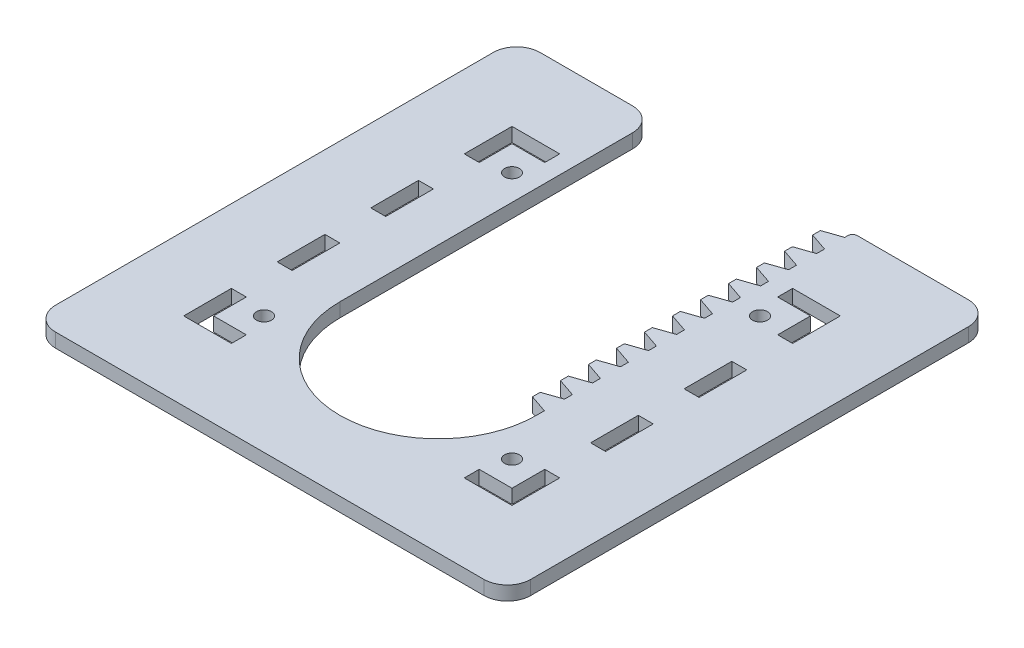
SolidWorks part; units mm, degrees
ref_plane "Front Plane" through (0, 0, 0) normal (0, 0, 1) x (1, 0, 0)
ref_plane "Top Plane" through (0, 0, 0) normal (0, 1, 0) x (1, 0, 0)
ref_plane "Right Plane" through (0, 0, 0) normal (1, 0, 0) x (0, 0, -1)
sketch "Sketch1" plane through (0, 0, 0) normal (0, 1, 0) x (1, 0, 0)
  line L0 (0, 0) -> (0, 21) construction
  line L1 (17.1887, 0) -> (0, 0) construction
  line L2 (21.0585, 3.843) -> (17.1887, 5.1665) construction
  line L3 (17.1887, 5.1665) -> (17.1887, 6.8335) construction
  line L4 (17.1887, 6.8335) -> (21.0585, 8.157) construction
  line L5 (21.0585, 9.843) -> (21.0585, 8.157) construction
  line L6 (21.0585, 9.843) -> (17.1887, 11.1665) construction
  line L7 (17.1887, 11.1665) -> (17.1887, 12.8335) construction
  line L8 (17.1887, 12.8335) -> (21.0585, 14.157) construction
  line L9 (21.0585, 15.843) -> (21.0585, 14.157) construction
  line L10 (21.0585, 15.843) -> (17.1887, 17.1665) construction
  line L11 (17.1887, 17.1665) -> (17.1887, 18.8335) construction
  line L12 (17.1887, 18.8335) -> (21.0585, 20.157) construction
  line L13 (21.0585, 21.843) -> (21.0585, 20.157) construction
  line L14 (21.0585, 21.843) -> (17.1887, 23.1665) construction
  line L15 (17.1887, 23.1665) -> (17.1887, 24.8335) construction
  line L16 (17.1887, 24.8335) -> (21.0585, 26.157) construction
  line L17 (21.0585, 27.843) -> (21.0585, 26.157) construction
  line L18 (21.0585, 27.843) -> (17.1887, 29.1665) construction
  line L19 (17.1887, 29.1665) -> (17.1887, 30.8335) construction
  line L20 (17.1887, 30.8335) -> (21.0585, 32.157) construction
  line L21 (21.0585, 33.843) -> (21.0585, 32.157) construction
  line L22 (21.0585, 33.843) -> (17.1887, 35.1665) construction
  line L23 (17.1887, 35.1665) -> (17.1887, 36.8335) construction
  line L24 (17.1887, 36.8335) -> (21.0585, 38.157) construction
  line L25 (21.0585, 39.843) -> (21.0585, 38.157) construction
  line L26 (21.0585, 39.843) -> (17.1887, 41.1665) construction
  line L27 (17.1887, 41.1665) -> (17.1887, 42.8335) construction
  line L28 (17.1887, 42.8335) -> (21.0585, 44.157) construction
  line L29 (21.0585, 45.843) -> (21.0585, 44.157) construction
  line L30 (21.0585, 45.843) -> (17.1887, 47.1665) construction
  line L31 (17.1887, 47.1665) -> (17.1887, 48.8335) construction
  line L32 (17.1887, 48.8335) -> (21.0585, 50.157) construction
  line L33 (21.0585, 51.843) -> (21.0585, 50.157) construction
  line L34 (21.0585, 51.843) -> (17.1887, 53.1665) construction
  line L35 (17.1887, 53.1665) -> (17.1887, 54.8335) construction
  line L36 (17.1887, 54.8335) -> (21.0585, 56.157) construction
  line L37 (21.0585, 57.843) -> (21.0585, 56.157) construction
  line L38 (21.0585, 57.843) -> (17.1887, 59.1665) construction
  line L39 (17.1887, 59.1665) -> (17.1887, 60.8335) construction
  line L40 (17.1887, 60.8335) -> (21.0585, 62.157) construction
  line L41 (21.0585, 62.157) -> (21.0585, 62.843) construction
  line L42 (45.8722, 63.843) -> (22.0585, 63.843) construction
  line L43 (50.8722, -34.9014) -> (50.8722, 58.843) construction
  line L44 (45.8722, -39.9014) -> (-45.8722, -39.9014) construction
  line L45 (-50.8722, 58.843) -> (-50.8722, -34.9014) construction
  line L46 (-45.8722, 63.843) -> (-22.0585, 63.843) construction
  line L47 (-21.0585, -3.843) -> (-21.0585, 62.843) construction
  line L48 (21.0585, -2.157) -> (21.0585, -3.843) construction
  line L49 (21.0585, -2.157) -> (17.1887, -0.8335) construction
  line L50 (17.1887, -0.8335) -> (17.1887, 0.8335) construction
  line L51 (17.1887, 0.8335) -> (21.0585, 2.157) construction
  line L52 (21.0585, 3.843) -> (21.0585, 2.157) construction
  line L53 (21.0585, 3.843) -> (17.1887, 5.1665)
  line L54 (17.1887, 5.1665) -> (17.1887, 6.8335)
  line L55 (17.1887, 6.8335) -> (21.0585, 8.157)
  line L56 (21.0585, 9.843) -> (21.0585, 8.157)
  line L57 (21.0585, 9.843) -> (17.1887, 11.1665)
  line L58 (17.1887, 11.1665) -> (17.1887, 12.8335)
  line L59 (17.1887, 12.8335) -> (21.0585, 14.157)
  line L60 (21.0585, 15.843) -> (21.0585, 14.157)
  line L61 (21.0585, 15.843) -> (17.1887, 17.1665)
  line L62 (17.1887, 17.1665) -> (17.1887, 18.8335)
  line L63 (17.1887, 18.8335) -> (21.0585, 20.157)
  line L64 (21.0585, 21.843) -> (21.0585, 20.157)
  line L65 (21.0585, 21.843) -> (17.1887, 23.1665)
  line L66 (17.1887, 23.1665) -> (17.1887, 24.8335)
  line L67 (17.1887, 24.8335) -> (21.0585, 26.157)
  line L68 (21.0585, 27.843) -> (21.0585, 26.157)
  line L69 (21.0585, 27.843) -> (17.1887, 29.1665)
  line L70 (17.1887, 29.1665) -> (17.1887, 30.8335)
  line L71 (17.1887, 30.8335) -> (21.0585, 32.157)
  line L72 (21.0585, 33.843) -> (21.0585, 32.157)
  line L73 (21.0585, 33.843) -> (17.1887, 35.1665)
  line L74 (17.1887, 35.1665) -> (17.1887, 36.8335)
  line L75 (17.1887, 36.8335) -> (21.0585, 38.157)
  line L76 (21.0585, 39.843) -> (21.0585, 38.157)
  line L77 (21.0585, 39.843) -> (17.1887, 41.1665)
  line L78 (17.1887, 41.1665) -> (17.1887, 42.8335)
  line L79 (17.1887, 42.8335) -> (21.0585, 44.157)
  line L80 (21.0585, 45.843) -> (21.0585, 44.157)
  line L81 (21.0585, 45.843) -> (17.1887, 47.1665)
  line L82 (17.1887, 47.1665) -> (17.1887, 48.8335)
  line L83 (17.1887, 48.8335) -> (21.0585, 50.157)
  line L84 (21.0585, 51.843) -> (21.0585, 50.157)
  line L85 (21.0585, 51.843) -> (17.1887, 53.1665)
  line L86 (17.1887, 53.1665) -> (17.1887, 54.8335)
  line L87 (17.1887, 54.8335) -> (21.0585, 56.157)
  line L88 (21.0585, 57.843) -> (21.0585, 56.157)
  line L89 (21.0585, 57.843) -> (17.1887, 59.1665)
  line L90 (17.1887, 59.1665) -> (17.1887, 60.8335)
  line L91 (17.1887, 60.8335) -> (21.0585, 62.157)
  line L92 (21.0585, 62.157) -> (21.0585, 62.843)
  line L93 (45.8722, 63.843) -> (22.0585, 63.843)
  line L94 (50.8722, -34.9014) -> (50.8722, 58.843)
  line L95 (45.8722, -39.9014) -> (-45.8722, -39.9014)
  line L96 (-50.8722, 58.843) -> (-50.8722, -34.9014)
  line L97 (-45.8722, 63.843) -> (-26.0585, 63.843)
  line L98 (-21.0585, -3.843) -> (-21.0585, 58.843)
  line L99 (21.0585, -2.157) -> (21.0585, -3.843)
  line L100 (21.0585, -2.157) -> (17.1887, -0.8335)
  line L101 (17.1887, -0.8335) -> (17.1887, 0.8335)
  line L102 (17.1887, 0.8335) -> (21.0585, 2.157)
  line L103 (21.0585, 3.843) -> (21.0585, 2.157)
  line L104 (0, 63.843) -> (0, -39.9014) construction
  line L105 (-51.8722, 11.9708) -> (51.8722, 11.9708) construction
  line L106 (0, 11.9708) -> (-51.8722, -39.9014) construction
  line L107 (51.8722, -24.9014) -> (-51.8722, -24.9014) construction
  line L108 (-36.8722, -39.9014) -> (-36.8722, 63.843) construction
  line L109 (36.8722, -39.9014) -> (36.8722, 63.843) construction
  line L110 (45.8722, -39.9014) -> (51.8722, -39.9014) construction
  line L111 (51.8722, -39.9014) -> (51.8722, 63.843) construction
  line L112 (51.8722, 63.843) -> (-51.8722, 63.843) construction
  line L113 (17.1887, 60) -> (0, 60) construction
  line L114 (-51.8722, 63.843) -> (-51.8722, -39.9014) construction
  line L115 (-51.8722, -39.9014) -> (-45.8722, -39.9014) construction
  circle A0 centre (0, 0) radius 21 construction
  circle A1 centre (0, 60) radius 21 construction
  arc A2 (22.0585, 63.843) -> (21.0585, 62.843) centre (22.0585, 62.843) ccw construction
  arc A3 (50.8722, 58.843) -> (45.8722, 63.843) centre (45.8722, 58.843) ccw construction
  arc A4 (45.8722, -39.9014) -> (50.8722, -34.9014) centre (45.8722, -34.9014) ccw construction
  arc A5 (-50.8722, -34.9014) -> (-45.8722, -39.9014) centre (-45.8722, -34.9014) ccw construction
  arc A6 (-45.8722, 63.843) -> (-50.8722, 58.843) centre (-45.8722, 58.843) ccw construction
  arc A8 (-21.0585, -3.843) -> (21.0585, -3.843) centre (0, -3.843) ccw construction
  arc A9 (22.0585, 63.843) -> (21.0585, 62.843) centre (22.0585, 62.843) ccw
  arc A10 (50.8722, 58.843) -> (45.8722, 63.843) centre (45.8722, 58.843) ccw
  arc A11 (45.8722, -39.9014) -> (50.8722, -34.9014) centre (45.8722, -34.9014) ccw
  arc A12 (-50.8722, -34.9014) -> (-45.8722, -39.9014) centre (-45.8722, -34.9014) ccw
  arc A13 (-45.8722, 63.843) -> (-50.8722, 58.843) centre (-45.8722, 58.843) ccw
  arc A14 (-21.0585, 58.843) -> (-26.0585, 63.843) centre (-26.0585, 58.843) ccw
  arc A15 (-21.0585, -3.843) -> (21.0585, -3.843) centre (0, -3.843) ccw
  circle A16 centre (26.5585, -14.5877) radius 1.6 construction
  circle A17 centre (-26.5585, -14.5877) radius 1.6 construction
  circle A18 centre (-26.5585, 38.5292) radius 1.6 construction
  circle A19 centre (26.5585, 38.5292) radius 1.6 construction
  circle A20 centre (26.5585, -14.5877) radius 1.6
  circle A21 centre (-26.5585, -14.5877) radius 1.6
  circle A22 centre (-26.5585, 38.5292) radius 1.6
  circle A23 centre (26.5585, 38.5292) radius 1.6
  circle A24 centre (0, 60) radius 21 construction
sketch "Sketch2" plane through (0, 0, 0) normal (0, 0, 1) x (1, 0, 0)
  line L0 (0, 0) -> (0, 3) construction
  line L1 (-50.8722, 0) -> (50.8722, 0)
  line L2 (-50.8722, 0) -> (-50.8722, 3)
  line L3 (-50.8722, 3) -> (50.8722, 3)
  line L4 (50.8722, 0) -> (50.8722, 3)
  line L5 (-50.8722, 3) -> (-51.8722, 3) construction
  line L6 (-51.8722, 3) -> (-51.8722, 3.75) construction
  line L7 (-51.8722, 3.75) -> (51.8722, 3.75) construction
  line L8 (51.8722, 3.75) -> (51.8722, 3) construction
  line L9 (51.8722, 3) -> (50.8722, 3) construction
  line L10 (50.8722, 0) -> (51.8722, 0) construction
  line L11 (51.8722, 0) -> (51.8722, -0.75) construction
  line L12 (51.8722, -0.75) -> (-51.8722, -0.75) construction
  line L13 (-51.8722, -0.75) -> (-51.8722, 0) construction
  line L14 (-51.8722, 0) -> (-50.8722, 0) construction
  line L15 (59.7, 47.7) -> (59.7, 44.7) construction
  dimension "D2" = 0.75
extrude "Boss-Extrude1" add sketch "Sketch1" along normal up to vertex (3 mm away) up to point (-50.8722, 3, 0)
ref_plane "edge" through (0, 0, -63.843) normal (0, 0, 1) x (1, 0, 0)
sketch "Sketch4" plane through (0, 0, 0) normal (0, 1, 0) x (1, 0, 0)
  line L12 (-25.0418, -23.0877) -> (-25.0418, -20.0877) construction
  line L13 (-15.0251, -23.0877) -> (-15.0251, -20.0877) construction
  line L14 (-5.0084, -23.0877) -> (-5.0084, -20.0877) construction
  line L15 (5.0084, -23.0877) -> (5.0084, -20.0877) construction
  line L16 (15.0251, -23.0877) -> (15.0251, -20.0877) construction
  line L17 (25.0418, -20.0877) -> (25.0418, -23.0877) construction
  line L18 (32.0585, -20.0877) -> (35.0585, -20.0877) construction
  line L30 (-25.0418, -23.0877) -> (-25.0418, -20.0877)
  line L31 (-15.0251, -23.0877) -> (-15.0251, -20.0877)
  line L32 (-5.0084, -23.0877) -> (-5.0084, -20.0877)
  line L33 (5.0084, -23.0877) -> (5.0084, -20.0877)
  line L34 (15.0251, -23.0877) -> (15.0251, -20.0877)
  line L35 (25.0418, -20.0877) -> (25.0418, -23.0877)
  line L36 (-35.0585, 47.0292) -> (35.0585, 47.0292) construction
  line L37 (-32.0585, 44.0292) -> (32.0585, 44.0292) construction
  line L38 (-32.0585, -20.0877) -> (-32.0585, 44.0292) construction
  line L39 (-35.0585, -23.0877) -> (-35.0585, 47.0292) construction
  line L40 (-32.0585, -20.0877) -> (32.0585, -20.0877) construction
  line L41 (-35.0585, -23.0877) -> (35.0585, -23.0877) construction
  line L42 (32.0585, -20.0877) -> (32.0585, 44.0292) construction
  line L43 (35.0585, -23.0877) -> (35.0585, 47.0292) construction
  line L44 (-35.0585, 47.0292) -> (35.0585, 47.0292)
  line L45 (-32.0585, 44.0292) -> (32.0585, 44.0292)
  line L46 (-32.0585, -20.0877) -> (-32.0585, 44.0292)
  line L47 (-35.0585, -23.0877) -> (-35.0585, 47.0292)
  line L48 (-32.0585, -20.0877) -> (32.0585, -20.0877)
  line L49 (-35.0585, -23.0877) -> (35.0585, -23.0877)
  line L50 (32.0585, -20.0877) -> (32.0585, 44.0292)
  line L51 (35.0585, -23.0877) -> (35.0585, 47.0292)
  line L52 (-23.0585, 44.0292) -> (-23.0585, 47.0292) construction
  line L53 (-23.0585, 44.0292) -> (-23.0585, 47.0292)
  line L54 (23.0585, 44.0292) -> (23.0585, 47.0292) construction
  line L55 (23.0585, 44.0292) -> (23.0585, 47.0292)
  line L56 (-32.0585, 44.0292) -> (-35.0585, 44.0292) construction
  line L57 (-25.0418, 47.0292) -> (-25.0418, 44.0292) construction
  line L58 (25.0418, 47.0292) -> (25.0418, 44.0292) construction
  line L59 (32.0585, 47.0292) -> (32.0585, 44.0292) construction
  line L66 (-32.0585, -20.0877) -> (-32.0585, -23.0877) construction
sketch "Sketch3" plane through (0, 0, 0) normal (0, 1, 0) x (1, 0, 0)
  line L0 (32.0585, 37.0125) -> (35.0585, 37.0125) construction
  line L1 (25.0418, 47.0292) -> (25.0418, 44.0292) construction
  line L2 (25.0418, 44.0292) -> (32.0585, 44.0292) construction
  line L3 (32.0585, 44.0292) -> (32.0585, 37.0125) construction
  line L4 (32.0585, 37.0125) -> (35.0585, 37.0125) construction
  line L5 (35.0585, 37.0125) -> (35.0585, 47.0292) construction
  line L6 (35.0585, 47.0292) -> (25.0418, 47.0292) construction
  line L7 (35.0585, -23.0877) -> (35.0585, 47.0292) construction
  line L8 (32.0585, 11.9708) -> (0, 11.9708) construction
  line L9 (0, 11.9708) -> (0, 44.0292) construction
  line L10 (32.0585, 11.9708) -> (0, 11.9708) construction
  line L11 (0, 11.9708) -> (0, 44.0292) construction
  line L13 (35.0585, 26.9958) -> (32.0585, 26.9958) construction
  line L14 (35.0585, 16.9791) -> (32.0585, 16.9791) construction
  line L15 (32.0585, -20.0877) -> (32.0585, 44.0292) construction
  line L16 (35.0585, 26.9958) -> (32.0585, 26.9958) construction
  line L17 (35.0585, 26.9958) -> (35.0585, 16.9791) construction
  line L18 (35.0585, 16.9791) -> (32.0585, 16.9791) construction
  line L19 (32.0585, 26.9958) -> (32.0585, 16.9791) construction
  line L20 (35.1585, 27.0958) -> (35.1585, 16.8791)
  line L21 (35.1585, 16.8791) -> (31.9585, 16.8791)
  line L22 (31.9585, 27.0958) -> (31.9585, 16.8791)
  line L23 (35.1585, 27.0958) -> (31.9585, 27.0958)
  line L24 (35.1585, 36.9125) -> (35.1585, 47.1292)
  line L25 (35.1585, 47.1292) -> (24.9418, 47.1292)
  line L26 (24.9418, 47.1292) -> (24.9418, 43.9292)
  line L27 (24.9418, 43.9292) -> (31.9585, 43.9292)
  line L28 (31.9585, 43.9292) -> (31.9585, 36.9125)
  line L29 (31.9585, 36.9125) -> (35.1585, 36.9125)
  line L30 (35.1585, -3.1543) -> (31.9585, -3.1543)
  line L31 (31.9585, -3.1543) -> (31.9585, 7.0624)
  line L32 (35.1585, 7.0624) -> (31.9585, 7.0624)
  line L33 (35.1585, -3.1543) -> (35.1585, 7.0624)
  line L34 (31.9585, -19.9877) -> (31.9585, -12.971)
  line L35 (24.9418, -19.9877) -> (31.9585, -19.9877)
  line L36 (24.9418, -23.1877) -> (24.9418, -19.9877)
  line L37 (35.1585, -23.1877) -> (24.9418, -23.1877)
  line L38 (35.1585, -12.971) -> (35.1585, -23.1877)
  line L39 (31.9585, -12.971) -> (35.1585, -12.971)
  line L40 (-31.9585, 43.9292) -> (-31.9585, 36.9125)
  line L41 (-24.9418, 43.9292) -> (-31.9585, 43.9292)
  line L42 (-24.9418, 47.1292) -> (-24.9418, 43.9292)
  line L43 (-35.1585, 47.1292) -> (-24.9418, 47.1292)
  line L44 (-35.1585, 36.9125) -> (-35.1585, 47.1292)
  line L45 (-31.9585, 36.9125) -> (-35.1585, 36.9125)
  line L46 (-35.1585, 27.0958) -> (-35.1585, 16.8791)
  line L47 (-35.1585, 16.8791) -> (-31.9585, 16.8791)
  line L48 (-31.9585, 27.0958) -> (-31.9585, 16.8791)
  line L49 (-35.1585, 27.0958) -> (-31.9585, 27.0958)
  line L50 (-35.1585, -3.1543) -> (-31.9585, -3.1543)
  line L51 (-31.9585, -3.1543) -> (-31.9585, 7.0624)
  line L52 (-35.1585, 7.0624) -> (-31.9585, 7.0624)
  line L53 (-35.1585, -3.1543) -> (-35.1585, 7.0624)
  line L54 (-35.1585, -12.971) -> (-35.1585, -23.1877)
  line L55 (-31.9585, -12.971) -> (-35.1585, -12.971)
  line L56 (-31.9585, -19.9877) -> (-31.9585, -12.971)
  line L57 (-24.9418, -19.9877) -> (-31.9585, -19.9877)
  line L58 (-24.9418, -23.1877) -> (-24.9418, -19.9877)
  line L59 (-35.1585, -23.1877) -> (-24.9418, -23.1877)
  dimension "D1" = 0.1
extrude "Cut-Extrude1" cut sketch "Sketch3" along normal through all
